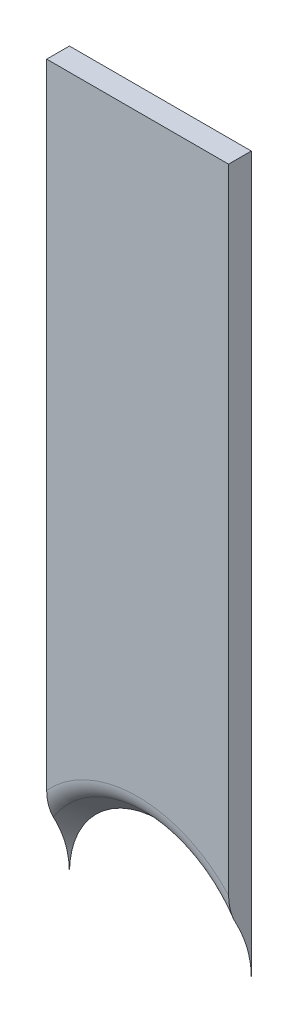
SolidWorks part; units mm, degrees
material "Acrylic (Medium-high impact)"
ref_plane "Front Plane" through (0, 0, 0) normal (0, 0, 1) x (1, 0, 0)
ref_plane "Top Plane" through (0, 0, 0) normal (0, 1, 0) x (1, 0, 0)
ref_plane "Right Plane" through (0, 0, 0) normal (1, 0, 0) x (0, 0, -1)
sketch "Sketch1" plane through (0, 0, 0) normal (0, 0, 1) x (1, 0, 0)
  line L1 (-40, -180) -> (40, -180)
  line L2 (-40, -180) -> (-40, 180)
  line L3 (-40, 180) -> (40, 180)
  line L4 (40, -180) -> (40, 180)
  line L5 (-40, -180) -> (40, 180) construction
  line L6 (-40, 180) -> (40, -180) construction
  point P0 (0, 0)
  dimension "D1" = 80
  dimension "D2" = 360
extrude "Boss-Extrude1" add sketch "Sketch1" along normal blind 10
sketch "Sketch2" plane through (0, 0, 10) normal (0, 0, 1) x (1, 0, 0)
  line L0 (-40, -180) -> (40, -180) construction
  line L1 (-40, -135) -> (-40, -180)
  line L2 (-40, -180) -> (40, -180)
  line L3 (40, -180) -> (40, -135)
  arc A0 (40, -135) -> (-40, -135) centre (0, -135) ccw
  dimension "D1" = 80
  dimension "D2" = 45
extrude "Cut-Extrude1" cut sketch "Sketch2" against normal blind 10
chamfer "Chamfer2" distance 10 angle 45 1 edges at (0, -95, 10)
fillet "Fillet1" radius 10 1 edges at (0, -85, 10)
